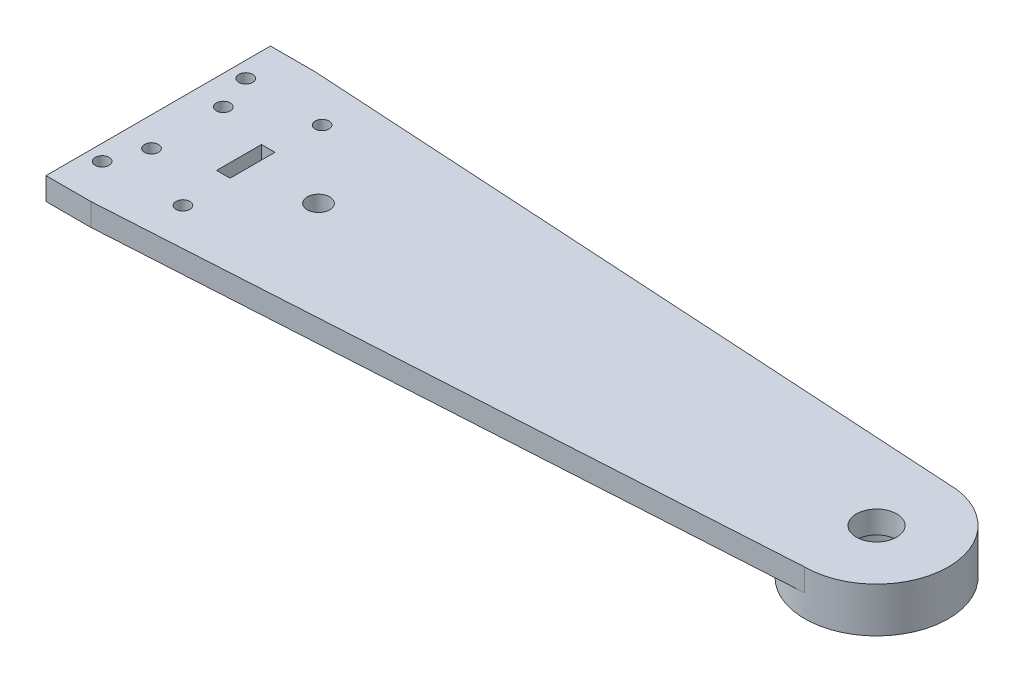
SolidWorks part; units mm, degrees
ref_plane "Front Plane" through (0, 0, 0) normal (0, 0, 1) x (1, 0, 0)
ref_plane "Top Plane" through (0, 0, 0) normal (0, 1, 0) x (1, 0, 0)
ref_plane "Right Plane" through (0, 0, 0) normal (1, 0, 0) x (0, 0, -1)
sketch "Sketch28" plane through (-32, 0, 0) normal (0, -1, 0) x (0, 0, 1)
  line L1 (0, -20.7) -> (0, -145) construction
  line L2 (-8, 8.5) -> (8, 8.5) construction
  line L3 (0, 15) -> (0, -3) construction
  line L8 (-25, 15) -> (25, 15)
  line L12 (25, 15) -> (25, 5)
  line L13 (-25, 15) -> (-25, 5)
  line L14 (-25, 5) -> (-16, -145)
  line L15 (16, -145) -> (25, 5)
  line L16 (-25, 5) -> (-25, 8.5) construction
  line L17 (-25, 8.5) -> (-8, 8.5) construction
  line L18 (-25, 15) -> (-25, 11.5) construction
  line L19 (-25, 11.5) -> (-16, 11.5) construction
  line L20 (-16, 11.5) -> (16, 11.5) construction
  line L21 (-5, -3) -> (5, -3)
  line L26 (5, -3) -> (5, -6)
  line L27 (5, -6) -> (-5, -6)
  line L28 (-5, -6) -> (-5, -3)
  line L29 (-5, -3) -> (-15.5, -3) construction
  line L30 (-15.5, -3) -> (-15.5, -6) construction
  line L31 (5, -3) -> (15.5, -3) construction
  line L32 (15.5, -3) -> (15.5, -6) construction
  line L33 (0, -20.7) -> (0, -6) construction
  circle A7 centre (8, 8.5) radius 1.55
  circle A8 centre (-8, 8.5) radius 1.55
  circle A9 centre (16, 11.5) radius 1.55
  circle A10 centre (-16, 11.5) radius 1.55
  circle A13 centre (-15.5, -6) radius 1.55
  circle A14 centre (15.5, -6) radius 1.55
  circle A15 centre (0, -20.7) radius 12.5 construction
  arc A17 (-16, -145) -> (16, -145) centre (0, -145) ccw
  circle A18 centre (0, -20.7) radius 2.5
  circle A19 centre (0, -145) radius 4.5
  point P13 (0, 15)
  point P27 (0, -3)
extrude "Boss-Extrude10" add sketch "Sketch28" along normal blind 5
sketch "Sketch29" plane through (0, -5, 0) normal (0, -1, 0) x (1, 0, 0)
  circle A0 centre (113, 0) radius 16
  circle A1 centre (113, 0) radius 8.2
  circle A2 centre (-11.3, 0) radius 6.7
  circle A3 centre (-11.3, 0) radius 10
extrude "Boss-Extrude11" add sketch "Sketch29" along normal blind 5
